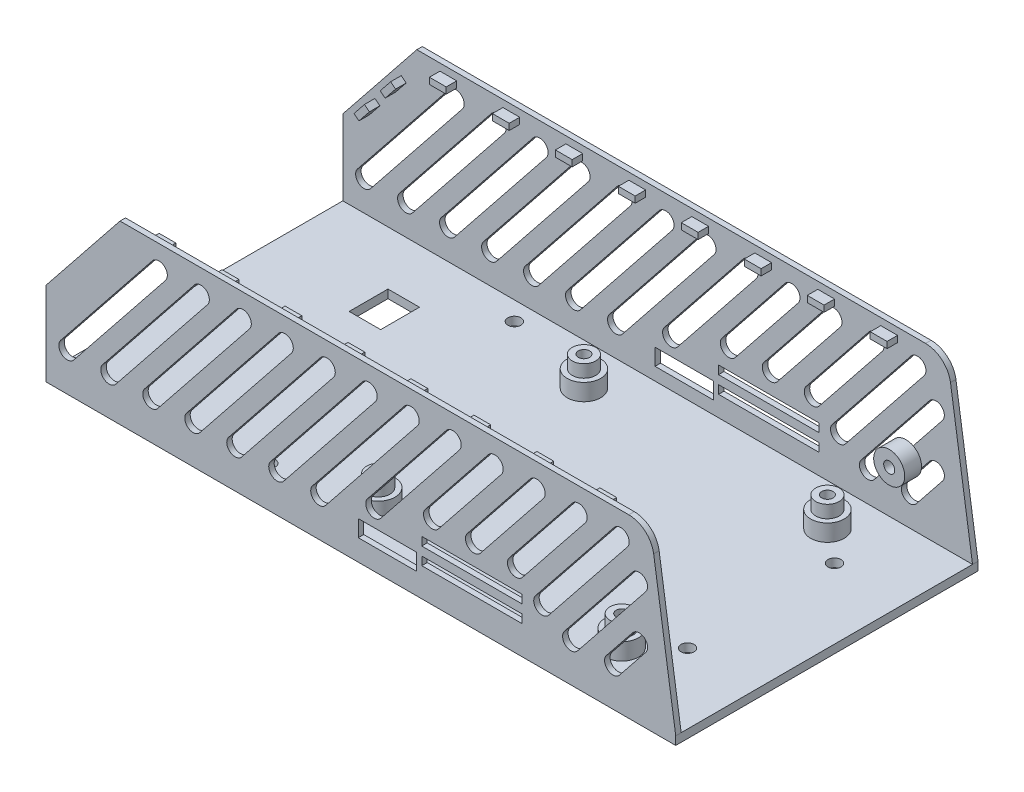
SolidWorks part; units mm, degrees
ref_plane "前视基准面" through (0, 0, 0) normal (0, 0, 1) x (1, 0, 0)
ref_plane "上视基准面" through (0, 0, 0) normal (0, 1, 0) x (1, 0, 0)
ref_plane "右视基准面" through (0, 0, 0) normal (1, 0, 0) x (0, 0, -1)
sketch "草图1" plane through (0, 0, 0) normal (0, 1, 0) x (1, 0, 0)
  line L1 (-38.5883, 74.1339) -> (111.4117, 74.1339)
  line L2 (-38.5883, 74.1339) -> (-38.5883, 2.1339)
  line L3 (-38.5883, 2.1339) -> (111.4117, 2.1339)
  line L4 (111.4117, 74.1339) -> (111.4117, 2.1339)
  dimension "D1" = 72
  dimension "D2" = 150
extrude "底板" add sketch "草图1" against normal blind 2 contours L2 L1 L4 L3
sketch "草图2" plane through (0, 0, 0) normal (0, 1, 0) x (1, 0, 0)
  circle A3 centre (28.7548, 13.929) radius 4
  circle A4 centre (86.7548, 13.929) radius 4
  circle A5 centre (86.7548, 62.929) radius 4
  circle A6 centre (28.7548, 62.929) radius 4
  dimension "D1" = 2
  dimension "D2" = 2
extrude "板卡固定柱" add sketch "草图2" along normal blind 7
sketch "螺母孔" plane through (0, -2, 0) normal (0, -1, 0) x (1, 0, 0)
  line L0 (88.7852, -11.7174) -> (85.8547, -11.0649)
  line L1 (30.7852, -11.7174) -> (27.8547, -11.0649)
  line L2 (27.8547, -11.0649) -> (25.8244, -13.2765)
  line L3 (25.8244, -13.2765) -> (26.7245, -16.1406)
  line L4 (26.7245, -16.1406) -> (29.655, -16.7931)
  line L5 (29.655, -16.7931) -> (31.6853, -14.5815)
  line L6 (31.6853, -14.5815) -> (30.7852, -11.7174)
  line L7 (85.8547, -11.0649) -> (83.8244, -13.2765)
  line L8 (83.8244, -13.2765) -> (84.7245, -16.1406)
  line L9 (84.7245, -16.1406) -> (87.655, -16.7931)
  line L10 (87.655, -16.7931) -> (89.6853, -14.5815)
  line L11 (89.6853, -14.5815) -> (88.7852, -11.7174)
  line L12 (88.7852, -60.7174) -> (85.8547, -60.0649)
  line L13 (85.8547, -60.0649) -> (83.8244, -62.2765)
  line L14 (83.8244, -62.2765) -> (84.7245, -65.1406)
  line L15 (84.7245, -65.1406) -> (87.655, -65.7931)
  line L16 (87.655, -65.7931) -> (89.6853, -63.5815)
  line L17 (89.6853, -63.5815) -> (88.7852, -60.7174)
  line L18 (30.7852, -60.7174) -> (27.8547, -60.0649)
  line L19 (27.8547, -60.0649) -> (25.8244, -62.2765)
  line L20 (25.8244, -62.2765) -> (26.7245, -65.1406)
  line L21 (26.7245, -65.1406) -> (29.655, -65.7931)
  line L22 (29.655, -65.7931) -> (31.6853, -63.5815)
  line L23 (31.6853, -63.5815) -> (30.7852, -60.7174)
  circle A0 centre (28.7548, -13.929) radius 2.6 construction
  circle A1 centre (28.7548, -13.929) radius 4 construction
  circle A2 centre (86.7548, -13.929) radius 2.6 construction
  circle A3 centre (86.7548, -62.929) radius 2.6 construction
  circle A4 centre (28.7548, -62.929) radius 2.6 construction
  dimension "D1" = 2
  dimension "D2" = 2
extrude "m2.5螺母孔槽" cut sketch "螺母孔" against normal blind 5
sketch "草图4" plane through (0, 3, 0) normal (0, -1, 0) x (1, 0, 0)
  circle A0 centre (28.7548, -13.929) radius 1.35
  circle A1 centre (28.7548, -13.929) radius 4 construction
  circle A2 centre (86.7548, -13.929) radius 1.35
  circle A3 centre (86.7548, -62.929) radius 1.35
  circle A4 centre (28.7548, -62.929) radius 1.35
  dimension "D1" = 2
  dimension "D2" = 2
extrude "m2.5通孔" cut sketch "草图4" against normal up to next
sketch "草图6" plane through (0, 7, 0) normal (0, 1, 0) x (1, 0, 0)
  circle A0 centre (28.7548, 13.929) radius 4
  circle A1 centre (28.7548, 13.929) radius 2.7944
  circle A2 centre (86.7548, 13.929) radius 4
  circle A3 centre (86.7548, 13.929) radius 2.7944
  circle A4 centre (86.7548, 62.929) radius 4
  circle A5 centre (86.7548, 62.929) radius 2.7944
  circle A6 centre (28.7548, 62.929) radius 4
  circle A7 centre (28.7548, 62.929) radius 2.7944
  dimension "D1" = 2
  dimension "D2" = 2
extrude "切除-拉伸3" cut sketch "草图6" against normal blind 3
sketch "侧边" plane through (0, 0, -74.1339) normal (0, 0, -1) x (-1, 0, 0)
  line L0 (-74.7943, 6.8381) -> (-50.9153, 6.8381)
  line L1 (-111.4117, 0) -> (38.5883, 0)
  line L6 (-74.7943, 10.8959) -> (-50.9153, 10.8959)
  line L8 (-74.7943, 10.8959) -> (-74.7943, 8.8959)
  line L9 (-74.7943, 4.8381) -> (-50.9153, 4.8381)
  line L10 (-50.9153, 4.8381) -> (-50.9153, 6.8381)
  line L11 (-74.7943, 8.8959) -> (-50.9153, 8.8959)
  line L12 (-74.7943, 6.8381) -> (-74.7943, 4.8381)
  line L13 (-50.9153, 8.8959) -> (-50.9153, 10.8959)
  line L16 (-49.6686, 3.0554) -> (-35.7948, 3.0554)
  line L17 (-35.7948, 3.0554) -> (-35.7948, 7)
  line L18 (-35.7948, 7) -> (-49.6686, 7)
  line L19 (-49.6686, 7) -> (-49.6686, 3.0554)
  line L20 (-88.7547, 7) -> (-26.2547, 7) construction
  line L21 (38.5883, -2) -> (38.5883, 0) construction
  line L22 (20.9589, 40) -> (-100.2254, 40)
  line L23 (-106.1585, 34.8932) -> (-111.4117, 0)
  line L25 (38.5883, 0) -> (38.5883, 17.9447)
  line L26 (38.5883, 17.9447) -> (20.9589, 40)
  line L27 (33.5375, 7.0719) -> (11.6845, 34.4113) construction
  line L28 (31.9753, 5.8231) -> (10.1222, 33.1625)
  line L29 (35.0998, 8.3206) -> (13.2467, 35.66)
  line L30 (23.5375, 7.0719) -> (1.6845, 34.4113) construction
  line L31 (21.9753, 5.8231) -> (0.1222, 33.1625)
  line L32 (25.0998, 8.3206) -> (3.2467, 35.66)
  line L33 (13.5375, 7.0719) -> (-8.3155, 34.4113) construction
  line L34 (11.9753, 5.8231) -> (-9.8778, 33.1625)
  line L35 (15.0998, 8.3206) -> (-6.7533, 35.66)
  line L36 (3.5375, 7.0719) -> (-18.3155, 34.4113) construction
  line L37 (1.9753, 5.8231) -> (-19.8778, 33.1625)
  line L38 (5.0998, 8.3206) -> (-16.7533, 35.66)
  line L39 (-6.4625, 7.0719) -> (-28.3155, 34.4113) construction
  line L40 (-8.0247, 5.8231) -> (-29.8778, 33.1625)
  line L41 (-4.9002, 8.3206) -> (-26.7533, 35.66)
  line L42 (-16.4625, 7.0719) -> (-38.3155, 34.4113) construction
  line L43 (-18.0247, 5.8231) -> (-39.8778, 33.1625)
  line L44 (-14.9002, 8.3206) -> (-36.7533, 35.66)
  line L45 (-26.4625, 7.0719) -> (-48.3155, 34.4113) construction
  line L46 (-28.0247, 5.8231) -> (-49.8778, 33.1625)
  line L47 (-24.9002, 8.3206) -> (-46.7533, 35.66)
  line L48 (-39.5843, 10.9775) -> (-58.3155, 34.4113) construction
  line L49 (-41.1466, 9.7287) -> (-59.8778, 33.1625)
  line L50 (-38.0221, 12.2262) -> (-56.7533, 35.66)
  line L51 (-53.3306, 15.6642) -> (-68.3155, 34.4113) construction
  line L52 (-54.8928, 14.4155) -> (-69.8778, 33.1625)
  line L53 (-51.7683, 16.913) -> (-66.7533, 35.66)
  line L54 (-63.3306, 15.6642) -> (-78.3155, 34.4113) construction
  line L55 (-64.8928, 14.4155) -> (-79.8778, 33.1625)
  line L56 (-61.7683, 16.913) -> (-76.7533, 35.66)
  line L57 (-73.3306, 15.6642) -> (-88.3155, 34.4113) construction
  line L58 (-74.8928, 14.4155) -> (-89.8778, 33.1625)
  line L59 (-71.7683, 16.913) -> (-86.7533, 35.66)
  line L60 (-79.5843, 10.9775) -> (-98.3155, 34.4113) construction
  line L61 (-81.1466, 9.7287) -> (-99.8778, 33.1625)
  line L62 (-78.0221, 12.2262) -> (-96.7533, 35.66)
  line L63 (-86.4625, 7.0719) -> (-102.6962, 27.3811) construction
  line L64 (-88.0247, 5.8231) -> (-104.2584, 26.1324)
  line L65 (-84.9002, 8.3206) -> (-101.1339, 28.6299)
  line L66 (-96.4625, 7.0719) -> (-102.7062, 14.8831) construction
  line L67 (-98.0247, 5.8231) -> (-104.2685, 13.6344)
  line L68 (-94.9002, 8.3206) -> (-101.144, 16.1319)
  arc A0 (-100.2254, 40) -> (-106.1585, 34.8932) centre (-100.2254, 34) ccw
  arc A1 (31.9753, 5.8231) -> (35.0998, 8.3206) centre (33.5375, 7.0719) ccw
  arc A2 (13.2467, 35.66) -> (10.1222, 33.1625) centre (11.6845, 34.4113) ccw
  arc A3 (21.9753, 5.8231) -> (25.0998, 8.3206) centre (23.5375, 7.0719) ccw
  arc A4 (3.2467, 35.66) -> (0.1222, 33.1625) centre (1.6845, 34.4113) ccw
  arc A5 (11.9753, 5.8231) -> (15.0998, 8.3206) centre (13.5375, 7.0719) ccw
  arc A6 (-6.7533, 35.66) -> (-9.8778, 33.1625) centre (-8.3155, 34.4113) ccw
  arc A7 (1.9753, 5.8231) -> (5.0998, 8.3206) centre (3.5375, 7.0719) ccw
  arc A8 (-16.7533, 35.66) -> (-19.8778, 33.1625) centre (-18.3155, 34.4113) ccw
  arc A9 (-8.0247, 5.8231) -> (-4.9002, 8.3206) centre (-6.4625, 7.0719) ccw
  arc A10 (-26.7533, 35.66) -> (-29.8778, 33.1625) centre (-28.3155, 34.4113) ccw
  arc A11 (-18.0247, 5.8231) -> (-14.9002, 8.3206) centre (-16.4625, 7.0719) ccw
  arc A12 (-36.7533, 35.66) -> (-39.8778, 33.1625) centre (-38.3155, 34.4113) ccw
  arc A13 (-28.0247, 5.8231) -> (-24.9002, 8.3206) centre (-26.4625, 7.0719) ccw
  arc A14 (-46.7533, 35.66) -> (-49.8778, 33.1625) centre (-48.3155, 34.4113) ccw
  arc A15 (-41.1466, 9.7287) -> (-38.0221, 12.2262) centre (-39.5843, 10.9775) ccw
  arc A16 (-56.7533, 35.66) -> (-59.8778, 33.1625) centre (-58.3155, 34.4113) ccw
  arc A17 (-54.8928, 14.4155) -> (-51.7683, 16.913) centre (-53.3306, 15.6642) ccw
  arc A18 (-66.7533, 35.66) -> (-69.8778, 33.1625) centre (-68.3155, 34.4113) ccw
  arc A19 (-64.8928, 14.4155) -> (-61.7683, 16.913) centre (-63.3306, 15.6642) ccw
  arc A20 (-76.7533, 35.66) -> (-79.8778, 33.1625) centre (-78.3155, 34.4113) ccw
  arc A21 (-74.8928, 14.4155) -> (-71.7683, 16.913) centre (-73.3306, 15.6642) ccw
  arc A22 (-86.7533, 35.66) -> (-89.8778, 33.1625) centre (-88.3155, 34.4113) ccw
  arc A23 (-81.1466, 9.7287) -> (-78.0221, 12.2262) centre (-79.5843, 10.9775) ccw
  arc A24 (-96.7533, 35.66) -> (-99.8778, 33.1625) centre (-98.3155, 34.4113) ccw
  arc A25 (-88.0247, 5.8231) -> (-84.9002, 8.3206) centre (-86.4625, 7.0719) ccw
  arc A26 (-101.1339, 28.6299) -> (-104.2584, 26.1324) centre (-102.6962, 27.3811) ccw
  arc A27 (-98.0247, 5.8231) -> (-94.9002, 8.3206) centre (-96.4625, 7.0719) ccw
  arc A28 (-101.144, 16.1319) -> (-104.2685, 13.6344) centre (-102.7062, 14.8831) ccw
  point P2 (22.611, 20.7416)
  point P31 (12.611, 20.7416)
  point P38 (2.611, 20.7416)
  point P48 (-7.389, 20.7416)
  point P55 (-17.389, 20.7416)
  point P62 (-27.389, 20.7416)
  point P69 (-37.389, 20.7416)
  point P76 (-48.9499, 22.6944)
  point P83 (-60.8231, 25.0378)
  point P90 (-70.8231, 25.0378)
  point P97 (-80.8231, 25.0378)
  point P104 (-88.9499, 22.6944)
  point P111 (-94.5793, 17.2265)
  point P118 (-99.5843, 10.9775)
  dimension "D1" = 6
  dimension "D2" = 40
extrude "侧边凸台" add sketch "侧边" against normal blind 1.3
sketch "草图14" plane through (0, 0, -72.8339) normal (0, 0, 1) x (1, 0, 0)
  line L0 (-30.9262, 24.9677) -> (-33.4237, 21.8432)
  line L1 (-33.4237, 21.8432) -> (-32.2521, 20.9067)
  line L2 (-24.6825, 32.779) -> (-27.18, 29.6545)
  line L3 (-27.18, 29.6545) -> (-26.0083, 28.7179)
  line L4 (-26.0083, 28.7179) -> (-23.5108, 31.8424)
  line L5 (-23.5108, 31.8424) -> (-24.6825, 32.779)
  line L6 (-32.2521, 20.9067) -> (-29.7546, 24.0312)
  line L7 (-29.7546, 24.0312) -> (-30.9262, 24.9677)
  line L9 (-15.4544, 38.32) -> (-11.4544, 38.32)
  line L10 (-11.4544, 38.32) -> (-11.4544, 36.82)
  line L11 (-11.4544, 36.82) -> (-15.4544, 36.82)
  line L12 (-15.4544, 36.82) -> (-15.4544, 38.32)
  line L13 (-20.9589, 40) -> (100.2254, 40) construction
  line L14 (-0.4544, 38.32) -> (3.5456, 38.32)
  line L15 (3.5456, 38.32) -> (3.5456, 36.82)
  line L16 (3.5456, 36.82) -> (-0.4544, 36.82)
  line L17 (-0.4544, 36.82) -> (-0.4544, 38.32)
  line L18 (14.5456, 38.32) -> (18.5456, 38.32)
  line L19 (18.5456, 38.32) -> (18.5456, 36.82)
  line L20 (18.5456, 36.82) -> (14.5456, 36.82)
  line L21 (14.5456, 36.82) -> (14.5456, 38.32)
  line L22 (29.5456, 38.32) -> (33.5456, 38.32)
  line L23 (33.5456, 38.32) -> (33.5456, 36.82)
  line L24 (33.5456, 36.82) -> (29.5456, 36.82)
  line L25 (29.5456, 36.82) -> (29.5456, 38.32)
  line L26 (44.5456, 38.32) -> (48.5456, 38.32)
  line L27 (48.5456, 38.32) -> (48.5456, 36.82)
  line L28 (48.5456, 36.82) -> (44.5456, 36.82)
  line L29 (44.5456, 36.82) -> (44.5456, 38.32)
  line L30 (59.5456, 38.32) -> (63.5456, 38.32)
  line L31 (63.5456, 38.32) -> (63.5456, 36.82)
  line L32 (63.5456, 36.82) -> (59.5456, 36.82)
  line L33 (59.5456, 36.82) -> (59.5456, 38.32)
  line L34 (74.5456, 38.32) -> (78.5456, 38.32)
  line L35 (78.5456, 38.32) -> (78.5456, 36.82)
  line L36 (78.5456, 36.82) -> (74.5456, 36.82)
  line L37 (74.5456, 36.82) -> (74.5456, 38.32)
  line L38 (89.5456, 38.32) -> (93.5456, 38.32)
  line L39 (93.5456, 38.32) -> (93.5456, 36.82)
  line L40 (93.5456, 36.82) -> (89.5456, 36.82)
  line L41 (89.5456, 36.82) -> (89.5456, 38.32)
  dimension "D1" = 2
  dimension "D2" = 1.68
  dimension "D3" = 1.5
  dimension "D4" = 4
  dimension "D5" = 8
extrude "顶盖支架" add sketch "草图14" along normal blind 2.5
sketch "草图15" plane through (0, -2, 0) normal (0, -1, 0) x (1, 0, 0)
  line L0 (-38.5883, -38.1339) -> (111.4117, -38.1339)
  line L1 (-38.5883, -74.1339) -> (-38.5883, -2.1339) construction
  line L2 (111.4117, -74.1339) -> (111.4117, -2.1339) construction
ref_plane "基准面7" through (0, 0, -38.1339) normal (0, 0, -1) x (-1, 0, 0)
mirror "镜向1" about plane through (0, 0, -38.1339) normal (0, 0, -1) of "侧边凸台", "顶盖支架"
sketch "草图17" plane through (0, -2, 0) normal (0, -1, 0) x (1, 0, 0)
  line L11 (-7.5182, -50.7739) -> (-15.0182, -50.7739)
  line L12 (-7.5182, -60.0239) -> (-7.5182, -50.7739)
  line L13 (-15.0182, -60.0239) -> (-7.5182, -60.0239)
  line L14 (-15.0182, -50.7739) -> (-15.0182, -60.0239)
  circle A6 centre (6.7318, -68.3739) radius 1.55
  circle A7 centre (94.7318, -56.6239) radius 1.55
  circle A8 centre (6.7318, -68.3739) radius 1.55
  circle A9 centre (94.7318, -21.6239) radius 1.55
  circle A10 centre (6.7318, -9.8739) radius 1.55
extrude "链接孔" cut sketch "草图17" against normal blind 2.5 contours A6 | L11 L14 L13 L12 | A7 | A9 | A10 region at (-11.2682, -2, -55.3989) region at (6.7318, -2, -68.3739)
sketch "草图10" plane through (0, 0, -72.8339) normal (0, 0, 1) x (1, 0, 0)
  circle A0 centre (95.5627, 14.116) radius 3.7
extrude "凸台-拉伸5" add sketch "草图10" along normal blind 4
sketch "草图11" plane through (0, 0, -68.8339) normal (0, 0, 1) x (1, 0, 0)
  circle A0 centre (95.5627, 14.116) radius 1.32
extrude "切除-拉伸4" cut sketch "草图11" against normal up to next
sketch "草图12" plane through (0, 0, -74.1339) normal (0, 0, -1) x (-1, 0, 0)
  circle A0 centre (-95.5627, 14.116) radius 2.5
ref_plane "基准面6" through (71.3625, -11, 47.1738) normal (-0.5878, 0, -0.809) x (-0.809, 0, 0.5878)
extrude "切除-拉伸5" cut sketch "草图12" against normal blind 3
sketch "草图8" plane through (0, 0, 0) normal (0, 1, 0) x (1, 0, 0)
  line L0 (86.7548, 62.929) -> (28.7548, 13.929)
  line L1 (28.7548, 13.929) -> (28.7548, 62.929)
  line L2 (28.7548, 62.929) -> (86.7548, 13.929)
  line L3 (86.7548, 13.929) -> (86.7548, 62.929)
